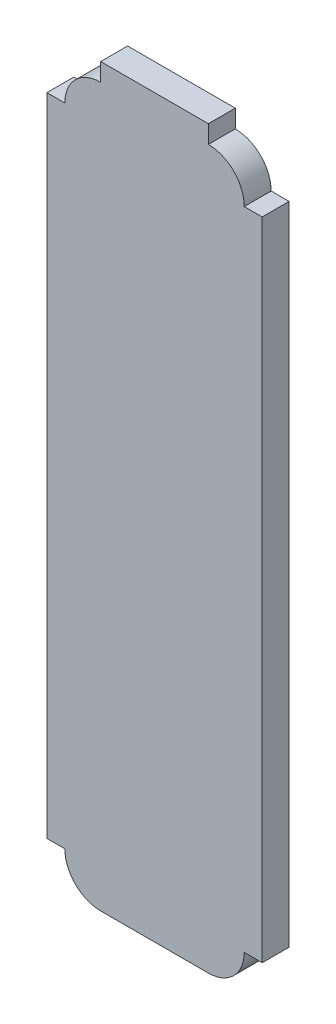
SolidWorks part; units mm, degrees
ref_plane "Płaszczyzna przednia" through (0, 0, 0) normal (0, 0, 1) x (1, 0, 0)
ref_plane "Płaszczyzna górna" through (0, 0, 0) normal (0, 1, 0) x (1, 0, 0)
ref_plane "Płaszczyzna prawa" through (0, 0, 0) normal (1, 0, 0) x (0, 0, -1)
sketch "Szkic1" plane through (0, 0, 0) normal (0, 0, 1) x (1, 0, 0)
  line L1 (0, 0) -> (10, 0)
  line L2 (0, 0) -> (0, 40)
  line L3 (0, 40) -> (10, 40)
  line L4 (10, 0) -> (10, 40)
  dimension "D1" = 10
  dimension "D2" = 40
extrude "Dodanie-wyciągnięcie1" add sketch "Szkic1" along normal blind 1.5
fillet "Zaokrąglenie1" radius 2 4 edges at (10, 0, 0.75) (0, 0, 0.75) (10, 40, 0.75) (0, 40, 0.75)
sketch "Szkic2" plane through (10, 0, 0) normal (1, 0, 0) x (0, 0, -1)
  line L1 (-1.5, 38) -> (0, 38)
  line L2 (-1.5, 38) -> (-1.5, 2)
  line L3 (-1.5, 2) -> (0, 2)
  line L4 (0, 38) -> (0, 2)
extrude "Dodanie-wyciągnięcie2" add sketch "Szkic2" along normal blind 1
sketch "Szkic3" plane through (0, 0, 0) normal (-1, 0, 0) x (0, 0, 1)
  line L1 (0, 38) -> (1.5, 38)
  line L2 (0, 38) -> (0, 2)
  line L3 (0, 2) -> (1.5, 2)
  line L4 (1.5, 38) -> (1.5, 2)
extrude "Dodanie-wyciągnięcie3" add sketch "Szkic3" along normal blind 1
sketch "Szkic4" plane through (0, 40, 0) normal (0, 1, 0) x (1, 0, 0)
  line L1 (2, 0) -> (8, 0)
  line L2 (2, 0) -> (2, -1.5)
  line L3 (2, -1.5) -> (8, -1.5)
  line L4 (8, 0) -> (8, -1.5)
extrude "Dodanie-wyciągnięcie4" add sketch "Szkic4" along normal blind 1
